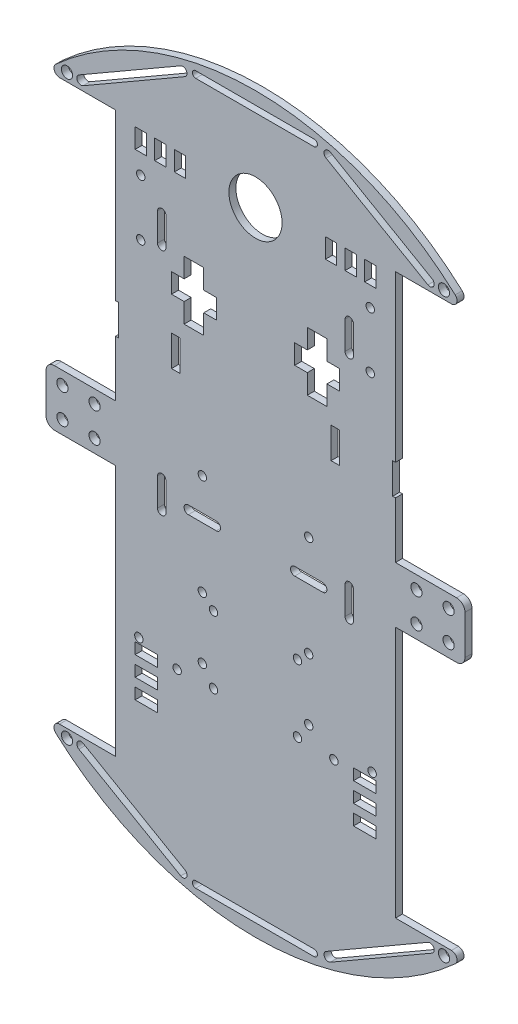
SolidWorks part; units mm, degrees
material "Acrylique (impact moyen-haut)"
ref_plane "Plan de face" through (0, 0, 0) normal (0, 0, 1) x (1, 0, 0)
ref_plane "Plan de dessus" through (0, 0, 0) normal (0, 1, 0) x (1, 0, 0)
ref_plane "Plan de droite" through (0, 0, 0) normal (1, 0, 0) x (0, 0, -1)
sketch "Esquisse1" plane through (0, 0, 0) normal (0, 0, 1) x (1, 0, 0)
  line L0 (100, 160.1886) -> (119.9942, 160.1886)
  line L1 (88.2026, 60.1886) -> (0, 60.1886) construction
  line L2 (0, -39.8114) -> (0, 50.1886)
  line L3 (0, 160.1886) -> (-19.9942, 160.1886)
  line L4 (100, -39.8114) -> (100, 50.1886)
  line L5 (125, 160.1886) -> (-25, 160.1886) construction
  line L6 (125, 191.1886) -> (-25, 191.1886) construction
  line L7 (50, -5.3114) -> (100, -5.3114) construction
  line L8 (50, 160.1886) -> (50, 128.9202) construction
  line L9 (50, 191.1886) -> (50, 60.1886) construction
  line L10 (50, 125.6886) -> (0, 125.6886) construction
  line L11 (50, 125.6886) -> (100, 125.6886) construction
  line L12 (50, -39.8114) -> (50, -8.5429) construction
  line L13 (0, -39.8114) -> (-19.9942, -39.8114)
  line L14 (100, -39.8114) -> (119.9942, -39.8114)
  line L15 (50, 191.1886) -> (50, -70.8114) construction
  line L16 (113.236, 70.1886) -> (113.236, 50.1886) construction
  line L17 (100, 50.1886) -> (121.8284, 50.1886)
  line L18 (100, 50.1886) -> (124.8284, 70.1886) construction
  line L19 (100, 70.1886) -> (121.8284, 70.1886)
  line L20 (124.8284, 53.1886) -> (124.8284, 67.1886)
  line L21 (100, 62.5) -> (124.8284, 70.1886) construction
  line L22 (100, 62.5) -> (124.8284, 50.1886) construction
  line L23 (124.8284, 50.1886) -> (100, 70.1886) construction
  line L24 (110.9672, 60.1886) -> (124.8284, 60.1886) construction
  line L25 (0, 50.1886) -> (-21.8284, 50.1886)
  line L26 (-24.8284, 53.1886) -> (-24.8284, 67.1886)
  line L27 (0, 70.1886) -> (-21.8284, 70.1886)
  line L28 (0, 70.1886) -> (0, 160.1886)
  line L29 (102.9549, 54.9) -> (118.9796, 65.4773) construction
  line L30 (102.9549, 65.4773) -> (118.9796, 54.9) construction
  line L31 (100, 70.1886) -> (100, 160.1886)
  arc A0 (121.3374, 163.6705) -> (-21.3374, 163.6705) centre (50, 84.9628) ccw
  arc A1 (119.9942, -39.8114) -> (121.3374, -43.2933) centre (119.9942, -41.8114) cw
  arc A2 (-21.3374, 163.6705) -> (-19.9942, 160.1886) centre (-19.9942, 162.1886) ccw
  arc A3 (119.9942, 160.1886) -> (121.3374, 163.6705) centre (119.9942, 162.1886) ccw
  arc A4 (-21.3374, -43.2933) -> (-19.9942, -39.8114) centre (-19.9942, -41.8114) cw
  arc A5 (121.3374, -43.2933) -> (-21.3374, -43.2933) centre (50, 35.4144) cw
  arc A6 (121.8284, 50.1886) -> (124.8284, 53.1886) centre (121.8284, 53.1886) ccw
  arc A7 (124.8284, 67.1886) -> (121.8284, 70.1886) centre (121.8284, 67.1886) ccw
  circle A8 centre (118.9796, 65.4773) radius 2
  circle A9 centre (107.4924, 54.9) radius 2
  circle A10 centre (118.9796, 54.9) radius 2
  circle A11 centre (107.4924, 65.4773) radius 2
  circle A12 centre (-7.4924, 54.9) radius 2
  arc A13 (-21.8284, 50.1886) -> (-24.8284, 53.1886) centre (-21.8284, 53.1886) cw
  circle A14 centre (-7.4924, 65.4773) radius 2
  circle A15 centre (-18.9796, 54.9) radius 2
  circle A16 centre (-18.9796, 65.4773) radius 2
  arc A17 (-24.8284, 67.1886) -> (-21.8284, 70.1886) centre (-21.8284, 67.1886) cw
  circle A18 centre (110.9672, 160.9487) radius 2
  circle A19 centre (-10.9672, 160.9487) radius 2
  circle A20 centre (110.9672, -40.5714) radius 2
  circle A21 centre (-10.9672, -40.5714) radius 2
  point P49 (110.9672, 60.1886)
  point P86 (0, 0)
  point P87 (0, 0)
  dimension "D3" = 3
  dimension "D5" = 31
  dimension "D1" = 2
  dimension "D6" = 4
  dimension "D7" = 4
  dimension "D2" = 20
  dimension "D4" = 150
  dimension "D8" = 90
  dimension "D9" = 90
extrude "Boss.-Extru.1" add sketch "Esquisse1" along normal blind 2.5 contours L4 L17 A6 L20 A7 L19 L31 L0 A3 A0 A2 L3 L28 L27 A17 L26 A13 L25 L2 L13 A4 A5 A1 L14
sketch "Esquisse2" plane through (0, 0, 0) normal (0, 0, -1) x (-1, 0, 0)
  line L0 (-100, 155) -> (0, 155) construction
  line L1 (-50, 155) -> (-50, 122.9953) construction
  line L2 (0, 5.1886) -> (-100, 5.1886) construction
  line L3 (0, -39.8114) -> (0, 50.1886) construction
  line L4 (-100, -39.8114) -> (-100, 50.1886) construction
  circle A0 centre (-50, 155) radius 9.5
  circle A1 centre (-50, -144.6227) radius 9.5
  point P6 (-50, 155)
  dimension "D1" = 19
extrude "Enlèv. mat.-Extru.1" cut sketch "Esquisse2" against normal through all
sketch "Esquisse3" plane through (0, 0, 0) normal (0, 0, -1) x (-1, 0, 0)
  line L1 (-93, 158.5) -> (-89, 158.5)
  line L2 (-93, 158.5) -> (-93, 151.5)
  line L3 (-93, 151.5) -> (-89, 151.5)
  line L4 (-89, 158.5) -> (-89, 151.5)
  line L5 (-100, -39.8114) -> (-100, 50.1886) construction
  line L11 (-100, 155) -> (-88.6993, 155) construction
  point P8 (-93, 155)
  dimension "D1" = 7
  dimension "D2" = 4
  dimension "D3" = 7
extrude "Enlèv. mat.-Extru.2" cut sketch "Esquisse3" against normal through all
pattern_linear "Répétition linéaire1" count 3 spacing 7 along (-1, 0, 0) of "Enlèv. mat.-Extru.2"
sketch "Esquisse4" plane through (0, 0, 0) normal (0, 0, -1) x (-1, 0, 0)
  line L0 (-75.5, 127.1886) -> (-68.5, 127.1886)
  line L1 (-68.5, 127.1886) -> (-68.5, 120.1886)
  line L2 (-68.5, 120.1886) -> (-64, 120.1886)
  line L3 (-64, 120.1886) -> (-64, 113.1886)
  line L4 (-64, 113.1886) -> (-68.5, 113.1886)
  line L5 (-68.5, 113.1886) -> (-68.5, 106.1886)
  line L6 (-68.5, 106.1886) -> (-75.5, 106.1886)
  line L7 (-75.5, 106.1886) -> (-75.5, 113.1886)
  line L8 (-75.5, 113.1886) -> (-80, 113.1886)
  line L9 (-80, 113.1886) -> (-80, 120.1886)
  line L10 (-80, 120.1886) -> (-75.5, 120.1886)
  line L11 (-75.5, 120.1886) -> (-75.5, 127.1886)
  line L12 (-100, 160.1886) -> (-119.9942, 160.1886) construction
  line L13 (-72, 127.1886) -> (-72, 106.1886) construction
  line L14 (-80, 116.6886) -> (-64, 116.6886) construction
  line L15 (-100, -39.8114) -> (-100, 50.1886) construction
  point P19 (-72, 116.6886)
  point P21 (-72, 116.6886)
  dimension "D1" = 47
  dimension "D2" = 7
  dimension "D3" = 16
  dimension "D4" = 21
  dimension "D5" = 7
  dimension "D6" = 20
extrude "Enlèv. mat.-Extru.3" cut sketch "Esquisse4" against normal through all
sketch "Esquisse5" plane through (0, 0, 0) normal (0, 0, -1) x (-1, 0, 0)
  line L0 (-80, 113.1886) -> (-75.5, 113.1886) construction
  line L1 (-80, 101.1886) -> (-77, 101.1886)
  line L2 (-80, 101.1886) -> (-80, 90.1886)
  line L3 (-80, 90.1886) -> (-77, 90.1886)
  line L4 (-77, 101.1886) -> (-77, 90.1886)
  line L5 (-100, -39.8114) -> (-100, 50.1886) construction
  dimension "D1" = 12
  dimension "D2" = 3
  dimension "D3" = 11
  dimension "D4" = 20
extrude "Enlèv. mat.-Extru.4" cut sketch "Esquisse5" against normal through all
pattern_linear "Répétition linéaire2" count 2 spacing 22 along (1, 0, 0) of "Enlèv. mat.-Extru.4"
sketch "Esquisse6" plane through (0, 0, 0) normal (0, 0, -1) x (-1, 0, 0)
  line L0 (-65, 22.6886) -> (-65, 7.0648) construction
  line L1 (-100, -39.8114) -> (-100, 50.1886) construction
  line L2 (-83.5, 54.5) -> (-83.5, 44.5) construction
  line L3 (-82, 54.5) -> (-82, 44.5)
  line L4 (-85, 54.5) -> (-85, 44.5)
  line L5 (-74, 49.5) -> (-64, 49.5) construction
  line L6 (-74, 51) -> (-64, 51)
  line L7 (-74, 48) -> (-64, 48)
  line L8 (-83.5, 136.5) -> (-83.5, 126.5) construction
  line L9 (-82, 136.5) -> (-82, 126.5)
  line L10 (-85, 136.5) -> (-85, 126.5)
  line L11 (-112.3374, 163.1886) -> (-75.9643, 184.1886) construction
  line L12 (-113.0874, 164.4877) -> (-76.7143, 185.4877)
  line L13 (-111.5874, 161.8896) -> (-75.2143, 182.8896)
  line L14 (-112.3374, 163.1886) -> (-68.1921, 163.1886) construction
  line L15 (-100, 160.1886) -> (-119.9942, 160.1886) construction
  line L16 (-91, 151.5) -> (-91, 144.5) construction
  line L17 (-93, 151.5) -> (-89, 151.5) construction
  line L18 (-50, 191.1886) -> (-50, -70.8114) construction
  line L19 (-69, 49.5) -> (-69, 65.1561) construction
  line L20 (-50, 89.2969) -> (-50, -6.5) construction
  line L21 (0, -39.8114) -> (0, 50.1886) construction
  line L22 (-50, 60.1886) -> (-124.8284, 60.1886) construction
  line L23 (-124.8284, 53.1886) -> (-124.8284, 67.1886) construction
  line L24 (-112.3374, -42.8114) -> (-75.9643, -63.8114) construction
  line L25 (-113.0874, -44.1104) -> (-76.7143, -65.1104)
  line L26 (-111.5874, -41.5123) -> (-75.2143, -62.5123)
  circle A0 centre (-91, 144.5) radius 1.5
  arc A1 (-82, 54.5) -> (-85, 54.5) centre (-83.5, 54.5) ccw
  circle A2 centre (-91, 124.5) radius 1.5
  circle A3 centre (-65, 22.6886) radius 1.5
  circle A4 centre (-69, 26.5) radius 1.5
  circle A5 centre (-91.6649, 1.1563) radius 1.5
  circle A6 centre (-77.9893, -1.8398) radius 1.5
  circle A7 centre (-69, 4.5) radius 1.5
  circle A8 centre (-65, -1.3114) radius 1.5
  arc A9 (-85, 44.5) -> (-82, 44.5) centre (-83.5, 44.5) ccw
  arc A10 (-74, 51) -> (-74, 48) centre (-74, 49.5) ccw
  arc A11 (-64, 48) -> (-64, 51) centre (-64, 49.5) ccw
  arc A12 (-82, 136.5) -> (-85, 136.5) centre (-83.5, 136.5) ccw
  arc A13 (-85, 126.5) -> (-82, 126.5) centre (-83.5, 126.5) ccw
  arc A14 (-113.0874, 164.4877) -> (-111.5874, 161.8896) centre (-112.3374, 163.1886) ccw
  arc A15 (-75.2143, 182.8896) -> (-76.7143, 185.4877) centre (-75.9643, 184.1886) ccw
  circle A16 centre (-69, 62.5) radius 1.5
  arc A17 (21.3374, 163.6705) -> (-121.3374, 163.6705) centre (-50, 84.9628) ccw construction
  arc A18 (-121.3374, -43.2933) -> (21.3374, -43.2933) centre (-50, 35.4144) ccw construction
  arc A19 (-113.0874, -44.1104) -> (-111.5874, -41.5123) centre (-112.3374, -42.8114) cw
  arc A20 (-75.2143, -62.5123) -> (-76.7143, -65.1104) centre (-75.9643, -63.8114) cw
  point P21 (-83.5, 49.5)
  point P26 (-69, 49.5)
  point P33 (-83.5, 131.5)
  point P40 (-94.1508, 173.6886)
  point P78 (-94.1508, -53.3114)
  dimension "D1" = 3
  dimension "D2" = 3
  dimension "D3" = 3
  dimension "D4" = 3
  dimension "D5" = 3
  dimension "D6" = 3
  dimension "D7" = 3
  dimension "D10" = 3
  dimension "D28" = 3
  dimension "D8" = 24
  dimension "D11" = 3
  dimension "D12" = 3
  dimension "D13" = 3
  dimension "D14" = 3
  dimension "D15" = 15
  dimension "D17" = 10
  dimension "D18" = 10
  dimension "D19" = 10
  dimension "D20" = 42
  dimension "D21" = 3
  dimension "D22" = 9
  dimension "D23" = 30
  dimension "D24" = 7
  dimension "D25" = 15
  dimension "D26" = 20
  dimension "D27" = 72
  dimension "D16" = 8
  dimension "D29" = 11.5
  dimension "D30" = 21.5
  dimension "D31" = 137.5
  dimension "D9" = 15
  dimension "D32" = 14
  dimension "D33" = 13
  dimension "D34" = 11
  dimension "D35" = 22
  dimension "D36" = 34
extrude "Enlèv. mat.-Extru.5" cut sketch "Esquisse6" against normal through all
sketch "Esquisse7" plane through (0, 0, 0) normal (0, 0, -1) x (-1, 0, 0)
  line L0 (-100, -39.8114) -> (-100, 50.1886) construction
  line L1 (-100, -39.8114) -> (-119.9942, -39.8114) construction
  line L5 (-93, -0.8114) -> (-85, -0.8114)
  line L6 (-93, -0.8114) -> (-93, -4.8114)
  line L7 (-93, -4.8114) -> (-85, -4.8114)
  line L8 (-85, -0.8114) -> (-85, -4.8114)
  line L9 (-93, -7.8114) -> (-85, -7.8114)
  line L10 (-93, -7.8114) -> (-93, -11.8114)
  line L11 (-93, -11.8114) -> (-85, -11.8114)
  line L12 (-85, -7.8114) -> (-85, -11.8114)
  line L13 (-93, -14.8114) -> (-85, -14.8114)
  line L14 (-93, -14.8114) -> (-93, -18.8114)
  line L15 (-93, -18.8114) -> (-85, -18.8114)
  line L16 (-85, -14.8114) -> (-85, -18.8114)
  dimension "D6" = 3
  dimension "D7" = 3
  dimension "D1" = 4
  dimension "D2" = 4
  dimension "D3" = 4
  dimension "D4" = 8
  dimension "D5" = 7
  dimension "D8" = 21
extrude "Enlèv. mat.-Extru.6" cut sketch "Esquisse7" against normal through all
ref_plane "Plan1" through (50, 0, 0) normal (1, 0, 0) x (0, 0, -1)
mirror "Symétrie1" about plane through (50, 0, 0) normal (1, 0, 0) of "Répétition linéaire2", "Enlèv. mat.-Extru.2", "Répétition linéaire1", "Enlèv. mat.-Extru.3", "Enlèv. mat.-Extru.4", "Enlèv. mat.-Extru.5", "Enlèv. mat.-Extru.6"
sketch "Sketch1" plane through (0, 0, 0) normal (0, 0, -1) x (-1, 0, 0)
  line L0 (-50, 191.1886) -> (-50, -70.8114) construction
  line L1 (-50, 60.1886) -> (-124.8284, 60.1886) construction
  line L2 (-124.8284, 53.1886) -> (-124.8284, 67.1886) construction
  circle A0 centre (17.3275, 163.1886) radius 2
  arc A1 (21.3374, 163.6705) -> (-121.3374, 163.6705) centre (-50, 84.9628) ccw construction
  arc A2 (-121.3374, -43.2933) -> (21.3374, -43.2933) centre (-50, 35.4144) ccw construction
  circle A3 centre (-117.3275, 163.1886) radius 2
  circle A4 centre (-117.3275, -42.8114) radius 2
  circle A5 centre (17.3275, -42.8114) radius 2
  dimension "D1" = 4
  dimension "D2" = 28
extrude "Cut-Extrude1" cut sketch "Sketch1" against normal through all
extrude "Cut-Extrude3" cut sketch "Esquisse1<3>" against normal through all and the other way through all contours A11 | A8 | A10 | A9 | A16 | A15 | A14 | A12 region at (118.9796, 65.4773, 0) region at (107.4924, 54.9, 0) region at (118.9796, 54.9, 0) region at (107.4924, 65.4773, 0) region at (-7.4924, 65.4773, 0) region at (-18.9796, 54.9, 0) region at (-18.9796, 65.4773, 0)
sketch "Esquisse1<3>" plane through (0, 0, 0) normal (0, 0, 1) x (1, 0, 0) same geometry as "Esquisse1"
sketch "Sketch2" plane through (0, 0, 0) normal (0, 0, -1) x (-1, 0, 0)
  line L1 (-70.9454, 185.4693) -> (-28.619, 185.4693) construction
  line L2 (-70.9454, 186.6473) -> (-28.619, 186.6473)
  line L3 (-70.9454, 184.2913) -> (-28.619, 184.2913)
  line L4 (-124.8284, 60.1886) -> (-12.8487, 60.1886) construction
  line L5 (-124.8284, 53.1886) -> (-124.8284, 67.1886) construction
  line L6 (-70.9454, -65.092) -> (-28.619, -65.092) construction
  line L7 (-70.9454, -66.2701) -> (-28.619, -66.2701)
  line L8 (-70.9454, -63.914) -> (-28.619, -63.914)
  arc A0 (-70.9454, 186.6473) -> (-70.9454, 184.2913) centre (-70.9454, 185.4693) ccw
  arc A1 (-28.619, 184.2913) -> (-28.619, 186.6473) centre (-28.619, 185.4693) ccw
  arc A2 (-70.9454, -66.2701) -> (-70.9454, -63.914) centre (-70.9454, -65.092) cw
  arc A3 (-28.619, -63.914) -> (-28.619, -66.2701) centre (-28.619, -65.092) cw
  point P2 (-49.7822, 185.4693)
  point P13 (-49.7822, -65.092)
  dimension "D1" = 1.178
extrude "Cut-Extrude4" cut sketch "Sketch2" against normal through all
equation "\"D2@Esquisse6\"=\"D1@Esquisse6\""
equation "\"D3@Esquisse6\"=\"D2@Esquisse6\""
equation "\"D4@Esquisse6\"=\"D2@Esquisse6\""
equation "\"D5@Esquisse6\"=\"D2@Esquisse6\""
equation "\"D6@Esquisse6\"=\"D2@Esquisse6\""
equation "\"D7@Esquisse6\"=\"D2@Esquisse6\""
equation "\"D2@Esquisse7\"=\"D1@Esquisse7\""
equation "\"D3@Esquisse7\"=\"D1@Esquisse7\""
equation "\"D10@Esquisse6\"=\"D7@Esquisse6\""
equation "\"D12@Esquisse6\"=\"D11@Esquisse6\""
equation "\"D13@Esquisse6\"=\"D11@Esquisse6\""
equation "\"D14@Esquisse6\"=\"D11@Esquisse6\""
equation "\"D17@Esquisse6\"=\"D19@Esquisse6\""
equation "\"D18@Esquisse6\"=\"D19@Esquisse6\""
equation "\"D28@Esquisse6\"=\"D1@Esquisse6\""
